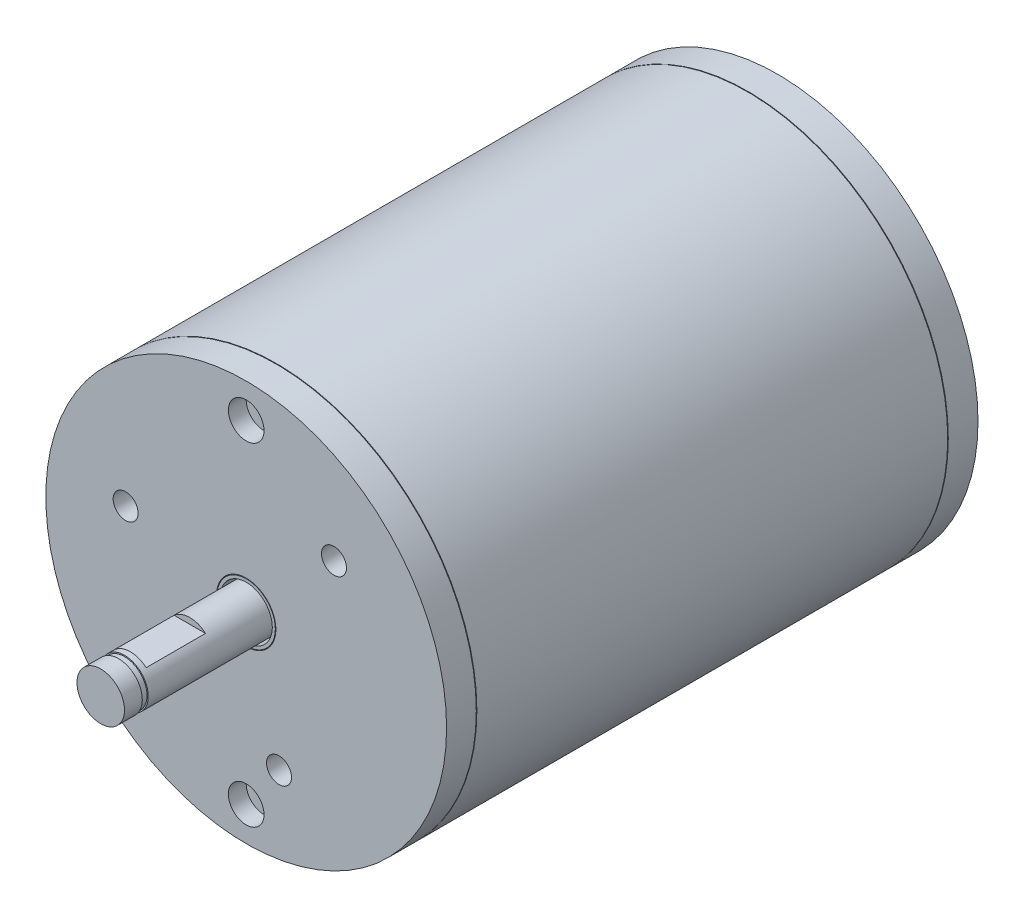
SolidWorks part; units mm, degrees
ref_plane "Front Plane" through (0, 0, 0) normal (0, 0, 1) x (1, 0, 0)
ref_plane "Top Plane" through (0, 0, 0) normal (0, 1, 0) x (1, 0, 0)
ref_plane "Right Plane" through (0, 0, 0) normal (1, 0, 0) x (0, 0, -1)
sketch "Sketch1" plane through (0, 0, 0) normal (0, 0, 1) x (1, 0, 0)
  circle A0 centre (0, 0) radius 33.75
  dimension "D1" = 67.5
extrude "Boss-Extrude1" add sketch "Sketch1" along normal blind 5
sketch "Sketch2" plane through (0, 0, 5) normal (0, 0, 1) x (1, 0, 0)
  circle A0 centre (0, 0) radius 33.6
  dimension "D1" = 67.2
extrude "Boss-Extrude2" add sketch "Sketch2" along normal blind 0.1
sketch "Sketch3" plane through (0, 0, 5.1) normal (0, 0, 1) x (1, 0, 0)
  circle A0 centre (0, 0) radius 33.75
  dimension "D1" = 67.5
extrude "Boss-Extrude3" add sketch "Sketch3" along normal blind 79.3
sketch "Sketch4" plane through (0, 0, 84.4) normal (0, 0, 1) x (1, 0, 0)
  circle A0 centre (0, 0) radius 33.6
  dimension "D1" = 67.2
extrude "Boss-Extrude4" add sketch "Sketch4" along normal blind 0.1
sketch "Sketch5" plane through (0, 0, 84.5) normal (0, 0, 1) x (1, 0, 0)
  circle A0 centre (0, 0) radius 33.75
  dimension "D1" = 67.5
extrude "Boss-Extrude5" add sketch "Sketch5" along normal blind 5
sketch "Sketch6" plane through (0, 0, 89.5) normal (0, 0, 1) x (1, 0, 0)
  circle A0 centre (0, 0) radius 21 construction
  circle A1 centre (14.3312, 15.3498) radius 2.1 construction
  circle A2 centre (6.1277, -20.0861) radius 2.1 construction
  circle A3 centre (-20.4589, 4.7363) radius 2.1 construction
  circle A4 centre (0, 0) radius 5
  dimension "D1" = 42
  dimension "D2" = 4.2
  dimension "D4" = 10
  dimension "D3" = 3
extrude "Cut-Extrude1" cut sketch "Sketch6" against normal blind 5
sketch "Sketch7" plane through (0, 0, 84.5) normal (0, 0, 1) x (1, 0, 0)
  circle A0 centre (0, 0) radius 4.9
  circle A1 centre (0, 0) radius 4.4
  dimension "D1" = 9.8
  dimension "D2" = 0.5
extrude "Boss-Extrude6" add sketch "Sketch7" along normal blind 5
sketch "Sketch8" plane through (0, 0, 84.5) normal (0, 0, 1) x (1, 0, 0)
  circle A0 centre (0, 0) radius 4
  dimension "D1" = 8
extrude "Boss-Extrude7" add sketch "Sketch8" along normal blind 24.5
sketch "Sketch9" plane through (0, 0, 0) normal (0, 0, -1) x (-1, 0, 0)
  circle A0 centre (0, 0) radius 15
  dimension "D1" = 30
extrude "Boss-Extrude8" add sketch "Sketch9" along normal blind 9.91
sketch "Sketch10" plane through (0, 0, 89.5) normal (0, 0, 1) x (1, 0, 0)
  circle A0 centre (0, 0) radius 21 construction
  circle A1 centre (14.7831, 14.9151) radius 1.75 construction
  circle A2 centre (5.5253, -20.2601) radius 1.75 construction
  circle A3 centre (-20.3084, 5.345) radius 1.75 construction
  dimension "D1" = 42
  dimension "D2" = 3.5
  dimension "D3" = 3
hole_wizard "M5 Tapped Hole1" positions "3DSketch1" profile "Sketch11" tap size "M5" standard "ISO"
sketch3d "3DSketch1"
  point P0 (-20.3084, 5.345, 89.5)
  point P3 (14.7831, 14.9151, 89.5)
  point P6 (5.5253, -20.2601, 89.5)
sketch "Sketch11" plane through (-20.3084, 5.345, 89.5) normal (1, 0, 0) x (0, -1, 0)
  line L0 (0, 0) -> (0, 6.2618)
  line L1 (0, 6.2618) -> (2.1, 5)
  line L2 (2.1, 5) -> (2.1, 0)
  line L5 (2.1, 0) -> (0, 0)
  line L10 (0, 6.2618) -> (-2.1, 5) construction
  line L11 (0, -6.35) -> (0, 107.95) construction
  dimension "Tap Drill Dia." = 4.2
  dimension "Tap Drill Depth" = 5
  dimension "Drill Angle" = 118
cosmetic thread "Hole Thread1" parameters "D1"=5, "D2"=5
cosmetic thread "Hole Thread2" parameters "D1"=5, "D2"=5
cosmetic thread "Hole Thread3" parameters "D1"=5, "D2"=5
ref_plane "Plane1" through (0, 4, 0) normal (0, 1, 0) x (1, 0, 0)
sketch "Sketch12" plane through (0, 4, 0) normal (0, 1, 0) x (1, 0, 0)
  line L1 (-4, -109) -> (4, -109)
  line L2 (-4, -109) -> (-4, -99)
  line L3 (-4, -99) -> (4, -99)
  line L4 (4, -109) -> (4, -99)
  dimension "D1" = 10
extrude "Cut-Extrude2" cut sketch "Sketch12" against normal blind 1 contours L4 L3 L2 L1
sketch "Sketch13" plane through (0, 0, 109) normal (0, 0, 1) x (1, 0, 0)
  circle A0 centre (0, 0) radius 4
extrude "Boss-Extrude9" add sketch "Sketch13" along normal blind 1
sketch "Sketch14" plane through (0, 0, 110) normal (0, 0, 1) x (1, 0, 0)
  circle A0 centre (0, 0) radius 3.8
  dimension "D1" = 7.6
extrude "Boss-Extrude10" add sketch "Sketch14" along normal blind 1
sketch "Sketch15" plane through (0, 0, 111) normal (0, 0, 1) x (1, 0, 0)
  circle A0 centre (0, 0) radius 4
  dimension "D1" = 8
extrude "Boss-Extrude11" add sketch "Sketch15" along normal blind 3
sketch "Sketch16" plane through (0, 0, 89.5) normal (0, 0, 1) x (1, 0, 0)
  circle A0 centre (0, 28) radius 3
  circle A1 centre (0, -28) radius 3
  dimension "D1" = 6
  dimension "D2" = 6
  dimension "D3" = 28
  dimension "D4" = 28
extrude "Cut-Extrude3" cut sketch "Sketch16" against normal blind 3
ref_plane "Plane2" through (0, 0, 110.5) normal (0, 0, 1) x (1, 0, 0)
ref_point "Point1"
ref_point "Point2"
ref_axis "Axis1" through (0, 0, -29.5916) along (0, 0, 1)
ref_point "Point3"
ref_plane "Plane3" through (0, 0, 0) normal (0.2545, 0.9671, 0) x (0.9671, -0.2545, 0)
